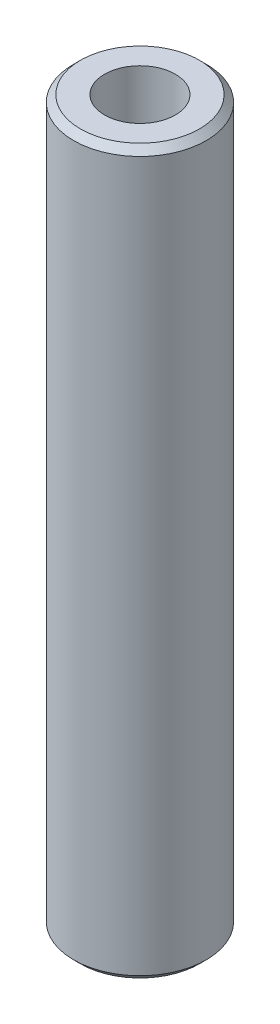
SolidWorks part; units mm, degrees
ref_plane "Front Plane" through (0, 0, 0) normal (0, 0, 1) x (1, 0, 0)
ref_plane "Top Plane" through (0, 0, 0) normal (0, 1, 0) x (1, 0, 0)
ref_plane "Right Plane" through (0, 0, 0) normal (1, 0, 0) x (0, 0, -1)
sketch "Sketch1" plane through (0, 0, 0) normal (0, 1, 0) x (1, 0, 0)
  circle A0 centre (0, 0) radius 55
  dimension "SHAFT_OD" = 110
extrude "Boss-Extrude1" add sketch "Sketch1" along normal blind 600
sketch "Sketch2" plane through (0, 0, 0) normal (0, 1, 0) x (1, 0, 0)
  circle A0 centre (0, 0) radius 29.3648
  dimension "BORE_D" = 58.7297
extrude "Cut-Extrude1" cut sketch "Sketch2" along normal through all
chamfer "Chamfer1" distance 5.6 angle 45 2 edges at (0, 600, 55) (0, 0, 55)
